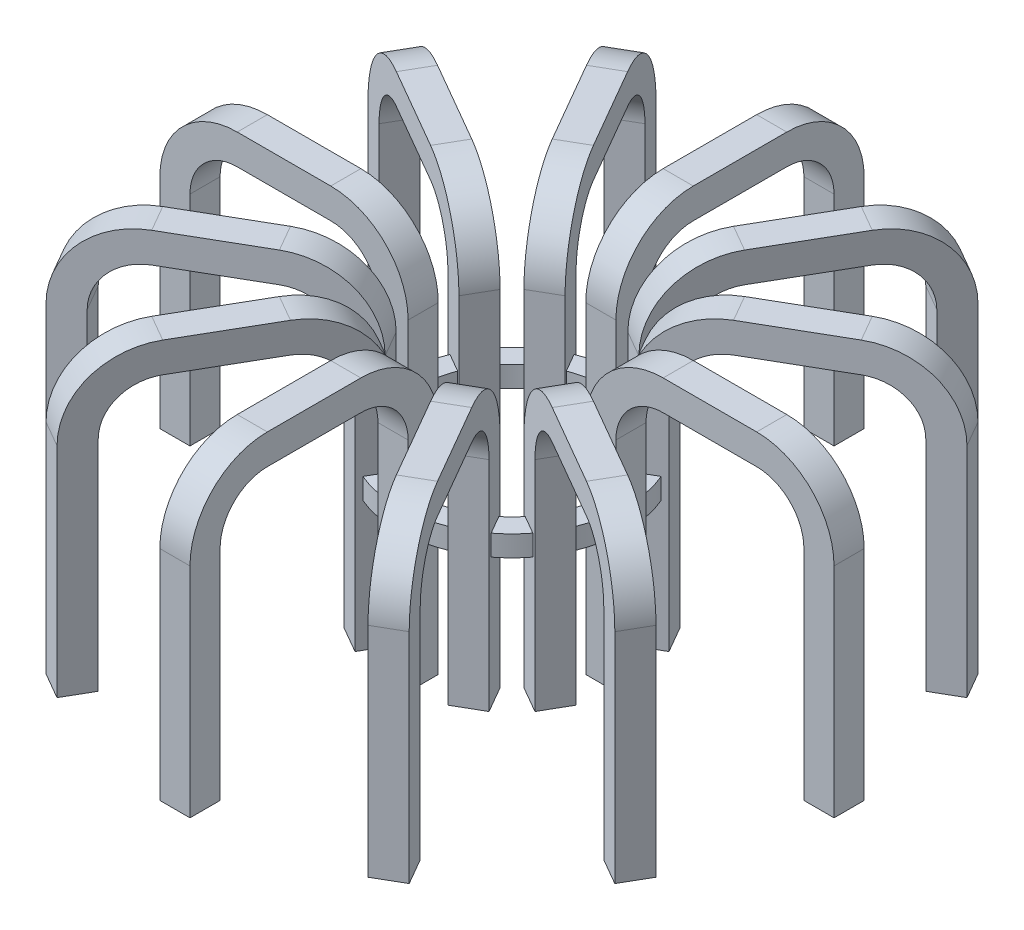
SolidWorks part; units mm, degrees
material "Copper"
ref_plane "Front Plane" through (0, 0, 0) normal (0, 0, 1) x (1, 0, 0)
ref_plane "Top Plane" through (0, 0, 0) normal (0, 1, 0) x (1, 0, 0)
ref_plane "Right Plane" through (0, 0, 0) normal (1, 0, 0) x (0, 0, -1)
other "Configuration Table"
sketch "Sketch3" plane through (0, 0, 0) normal (1, 0, 0) x (0, 0, -1)
  line L3 (-12.5, -5.25) -> (16.9772, -5.25) construction
  line L9 (12.5, 6.75) -> (10.25, 6.75)
  line L11 (15.5, -6.75) -> (15.5, 3.75)
  arc A7 (15.5, 3.75) -> (12.5, 6.75) centre (12.5, 3.75) ccw
  dimension "D3" = 1.5
ref_plane "Plane2" through (0, 0, -10.25) normal (0, 0, 1) x (1, 0, 0)
sketch "Sketch4" plane through (0, 0, -10.25) normal (0, 0, 1) x (1, 0, 0)
  line L0 (0.725, 7.475) -> (-0.725, 6.025) construction
  line L1 (-0.725, 7.475) -> (0.725, 7.475)
  line L2 (-0.725, 7.475) -> (-0.725, 6.025)
  line L3 (-0.725, 6.025) -> (0.725, 6.025)
  line L4 (0.725, 7.475) -> (0.725, 6.025)
  dimension "D1" = 1.45
  dimension "D2" = 1.45
sweep "Sweep1" add profiles "Sketch4" path "Sketch3"
mirror "Mirror1" about plane through (0, 0, -10.25) normal (0, 0, 1) of "Sweep1"
sketch "Sketch6" plane through (0, 0, 0) normal (1, 0, 0) x (0, 0, -1)
  line L0 (4.5, 0.5) -> (5.5, -0.5) construction
  line L1 (5.5, 0.5) -> (4.5, 0.5)
  line L2 (0, -3.6026) -> (0, 11.0757) construction
  line L3 (5, 0) -> (0, 0) construction
  line L4 (5.5, 0.5) -> (5.5, -0.5)
  line L5 (5.5, -0.5) -> (4.5, -0.5)
  line L6 (4.5, 0.5) -> (4.5, -0.5)
  point P9 (5, 0)
  dimension "D1" = 1
  dimension "D2" = 5
  dimension "D3" = 1
revolve "Revolve1" add sketch "Sketch6" angle 360 about L2
pattern_circular "CirPattern2" count 12 over 360 about axis through (0, -3.6026, 0) along (0, 1, 0) of bodies 102
combine bodies "Combine1" operation type add bodies to combine 102 122 124 125 126 127 128 129 130 131 132 134 133
